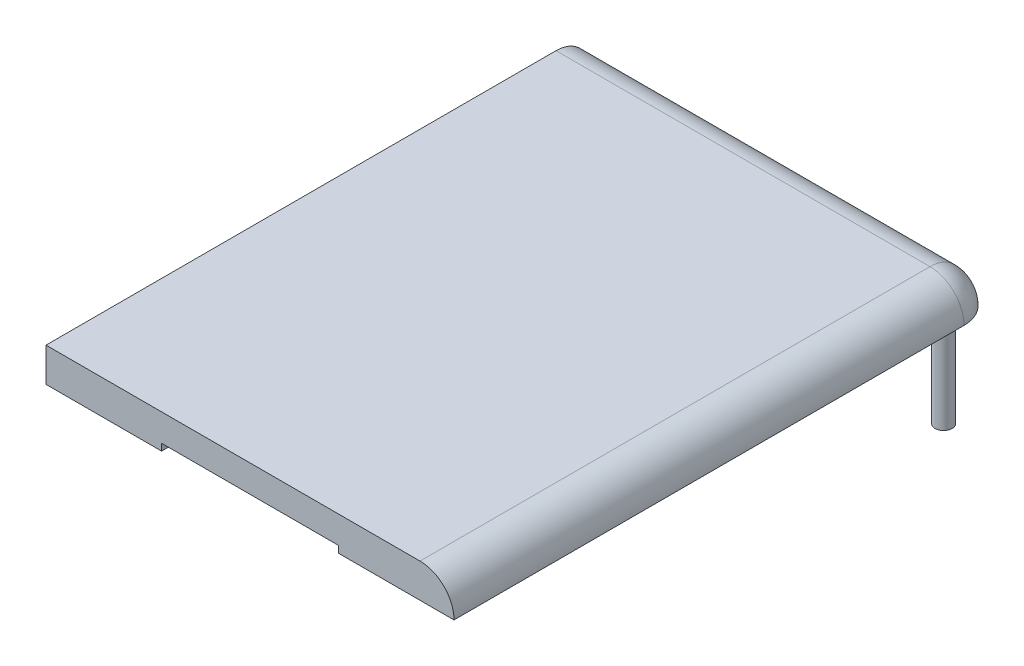
SolidWorks part; units mm, degrees
ref_plane "Plan de face" through (0, 0, 0) normal (0, 0, 1) x (1, 0, 0)
ref_plane "Plan de dessus" through (0, 0, 0) normal (0, 1, 0) x (1, 0, 0)
ref_plane "Plan de droite" through (0, 0, 0) normal (1, 0, 0) x (0, 0, -1)
sketch "Esquisse1" plane through (0, 0, 0) normal (0, 1, 0) x (1, 0, 0)
  line L1 (0, 0) -> (120, 0)
  line L2 (0, 0) -> (0, 160)
  line L3 (0, 160) -> (120, 160)
  line L4 (120, 0) -> (120, 160)
  dimension "D1" = 160
  dimension "D2" = 120
extrude "Boss.-Extru.1" add sketch "Esquisse1" along normal blind 10
fillet "Congé1" radius 10 1 edges at (120, 10, -80)
fillet "Congé2" radius 10 2 edges at (117.0711, 7.0711, -160) (55, 10, -160)
sketch "Esquisse2" plane through (0, 0, 0) normal (0, -1, 0) x (1, 0, 0)
  line L0 (110, -160) -> (0, -160) construction
  line L1 (120, 0) -> (120, -150) construction
  circle A0 centre (112, -152) radius 2.5
  dimension "D3" = 5
  dimension "D1" = 8
  dimension "D2" = 8
extrude "Boss.-Extru.2" add sketch "Esquisse2" along normal blind 30
sketch "Esquisse3" plane through (0, 0, 0) normal (0, -1, 0) x (1, 0, 0)
  line L0 (0, -160) -> (0, 0) construction
  line L1 (0, -106) -> (11, -106)
  line L2 (0, -106) -> (0, -54)
  line L3 (0, -54) -> (11, -54)
  line L4 (11, -106) -> (11, -54)
  line L5 (0, 0) -> (120, 0) construction
  line L6 (86, 0) -> (34, 0)
  line L7 (86, 0) -> (86, -11)
  line L8 (86, -11) -> (34, -11)
  line L9 (34, 0) -> (34, -11)
  line L10 (110, -160) -> (0, -160) construction
  line L11 (120, 0) -> (120, -150) construction
  dimension "D1" = 54
  dimension "D2" = 54
  dimension "D3" = 11
  dimension "D4" = 34
  dimension "D5" = 34
  dimension "D6" = 11
extrude "Enlèv. mat.-Extru.1" cut sketch "Esquisse3" against normal blind 2
